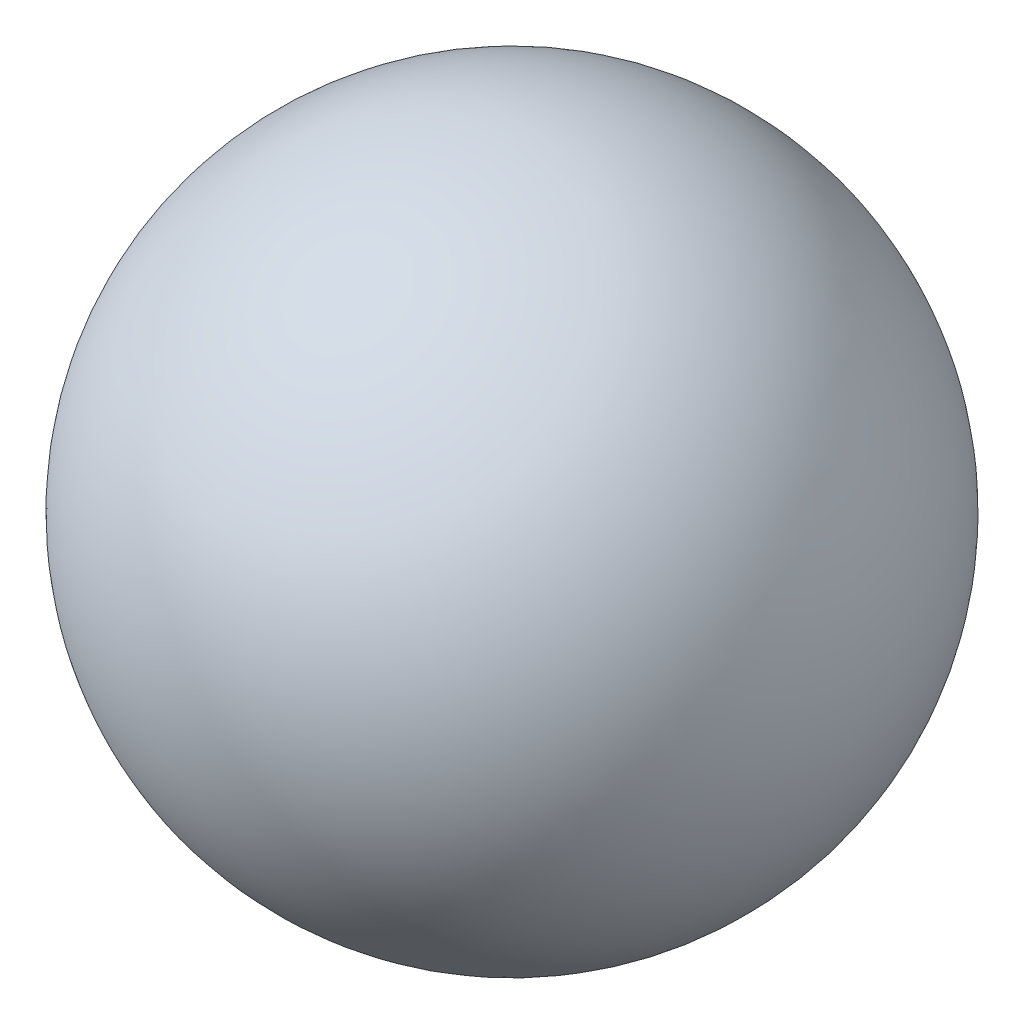
SolidWorks part; units mm, degrees
ref_plane "Front Plane" through (0, 0, 0) normal (0, 0, 1) x (1, 0, 0)
ref_plane "Top Plane" through (0, 0, 0) normal (0, 1, 0) x (1, 0, 0)
ref_plane "Right Plane" through (0, 0, 0) normal (1, 0, 0) x (0, 0, -1)
sketch "Sketch1" plane through (0, 0, 0) normal (0, 1, 0) x (1, 0, 0)
  line L0 (0, 34.25) -> (0, -34.25)
  arc A0 (0, 34.25) -> (0, -34.25) centre (0, 0) cw
  point P6 (0, 0)
  dimension "D1" = 34.25
revolve "Revolve1" add sketch "Sketch1" angle 360 about L0
